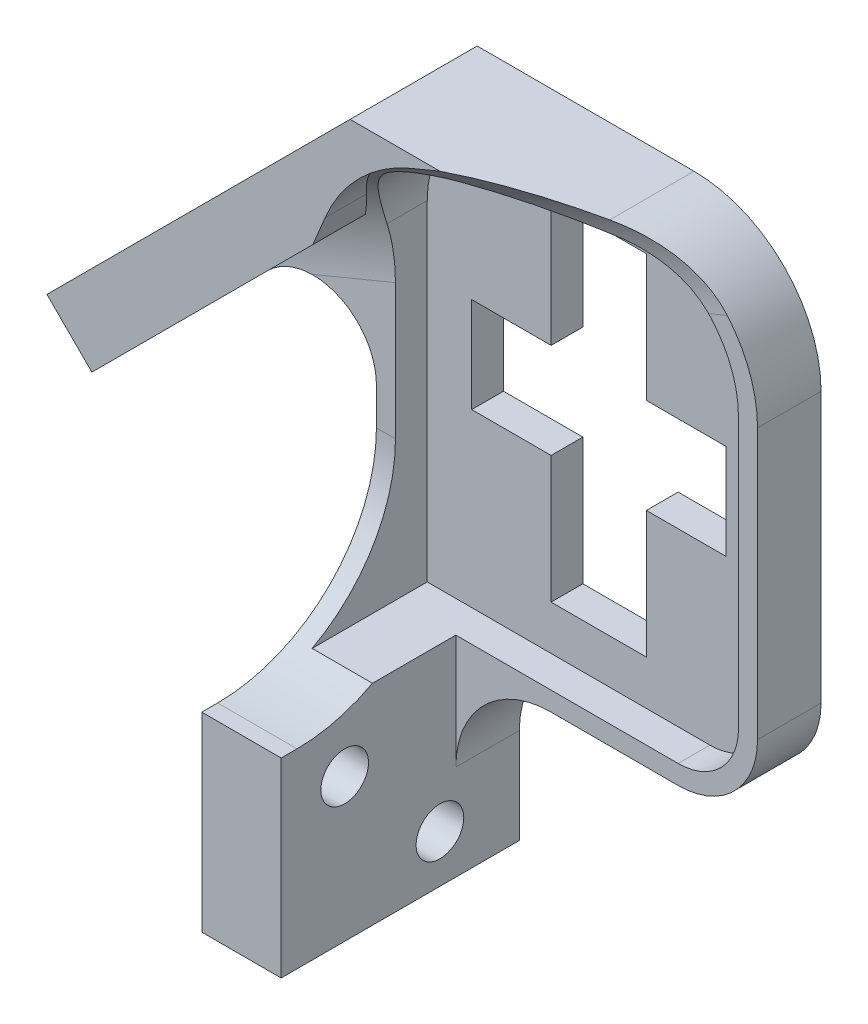
SolidWorks part; units mm, degrees
ref_plane "Front Plane" through (0, 0, 0) normal (0, 0, 1) x (1, 0, 0)
ref_plane "Top Plane" through (0, 0, 0) normal (0, 1, 0) x (1, 0, 0)
ref_plane "Right Plane" through (0, 0, 0) normal (1, 0, 0) x (0, 0, -1)
sketch "Sketch3" plane through (0, 0, 0) normal (0, 0, 1) x (1, 0, 0)
  line L0 (0, 10) -> (7, 10) construction
  line L1 (13, 4) -> (13, -13) construction
  line L2 (10, -16) -> (-7, -16) construction
  line L3 (-7, -16) -> (-7, 4) construction
  line L4 (-1, 10) -> (0, 10) construction
  line L5 (0, 0) -> (0, 10) construction
  line L6 (0, 12) -> (7, 12)
  line L7 (15, 4) -> (15, -13)
  line L8 (10, -18) -> (-9, -18)
  line L9 (-9, -18) -> (-9, 4)
  line L10 (-1, 12) -> (0, 12)
  arc A0 (13, 4) -> (7, 10) centre (7, 4) ccw construction
  arc A1 (-7, 4) -> (-1, 10) centre (-1, 4) cw construction
  arc A2 (10, -16) -> (13, -13) centre (10, -13) ccw construction
  arc A3 (15, 4) -> (7, 12) centre (7, 4) ccw
  arc A4 (10, -18) -> (15, -13) centre (10, -13) ccw
  arc A5 (-9, 4) -> (-1, 12) centre (-1, 4) cw
  point P9 (13, 10)
  point P12 (-7, 10)
  point P15 (13, -16)
  dimension "D5" = 6
  dimension "D6" = 3
  dimension "D1" = 10
  dimension "D2" = 26
  dimension "D3" = 20
  dimension "D4" = 7
  dimension "D7" = 2
extrude "Boss-Extrude4" add sketch "Sketch3" along normal blind 2
sketch "Sketch1" plane through (0, 0, 0) normal (0, 0, 1) x (1, 0, 0)
  line L0 (0, 0) -> (0, 8)
  line L1 (0, 8) -> (6, 8)
  line L2 (6, 8) -> (6, 0)
  line L3 (6, 0) -> (11, 0)
  line L4 (11, 0) -> (11, -6)
  line L5 (11, -6) -> (6, -6)
  line L6 (6, -6) -> (6, -14)
  line L7 (6, -14) -> (0, -14)
  line L8 (0, -14) -> (0, -6)
  line L9 (0, 0) -> (-5, 0)
  line L10 (-5, 0) -> (-5, -6)
  line L11 (-5, -6) -> (0, -6)
  dimension "D1" = 6
  dimension "D2" = 5
  dimension "D3" = 8
extrude "Cut-Extrude4" cut sketch "Sketch1" along normal blind 2
sketch "Sketch5" plane through (0, 0, 0) normal (0, 0, 1) x (1, 0, 0)
  line L0 (-9, -18) -> (-9, 4)
  line L2 (-9, -18) -> (10, -18)
  line L3 (-9, -18) -> (10, -18) construction
  line L4 (15, -13) -> (15, 4)
  line L5 (7, 12) -> (-1, 12)
  line L6 (7, 12) -> (-1, 12) construction
  line L7 (15, -13) -> (15, 4) construction
  line L8 (-7.8, -16.8) -> (-7.8, 4)
  line L9 (-7.8, -16.8) -> (10, -16.8)
  line L10 (13.8, -13) -> (13.8, 4)
  line L11 (7, 10.8) -> (-1, 10.8)
  arc A0 (-1, 12) -> (-9, 4) centre (-1, 4) ccw
  arc A1 (15, 4) -> (7, 12) centre (7, 4) ccw
  arc A2 (15, -13) -> (10, -18) centre (10, -13) cw
  arc A3 (-1, 10.8) -> (-7.8, 4) centre (-1, 4) ccw
  arc A4 (13.8, -13) -> (10, -16.8) centre (10, -13) cw
  arc A5 (13.8, 4) -> (7, 10.8) centre (7, 4) ccw
  point P18 (15, -18)
  dimension "D1" = 8
  dimension "D2" = 5
  dimension "D3" = 1.2
extrude "Boss-Extrude5" add sketch "Sketch5" along normal blind 4
sketch "Sketch6" plane through (0, -18, 0) normal (0, -1, 0) x (1, 0, 0)
  line L0 (-9, 0) -> (-4, 0)
  line L1 (-9, 0) -> (10, 0) construction
  line L2 (-4, 0) -> (-4, 15)
  line L3 (-9, 0) -> (-9, 15)
  line L4 (-9, 15) -> (-4, 15)
  dimension "D1" = 5
  dimension "D2" = 15
extrude "Boss-Extrude6" add sketch "Sketch6" along normal blind 12
fillet "Fillet1" radius 6 1 edges at (-4, -18, 2)
sketch "Sketch7" plane through (-4, 0, 0) normal (1, 0, 0) x (0, 0, -1)
  line L0 (-11, -21) -> (-5, -27) construction
  line L2 (-15, -30) -> (-15, -18) construction
  line L3 (-5, -27) -> (-11, -27) construction
  line L4 (-11, -27) -> (-11, -21) construction
  line L5 (-4, -18) -> (-15, -18) construction
  circle A0 centre (-11, -21) radius 1.5
  circle A1 centre (-5, -27) radius 1.5
  dimension "D1" = 3
  dimension "D2" = 6
  dimension "D3" = 3
  dimension "D4" = 45
  dimension "D6" = 4
extrude "Cut-Extrude5" cut sketch "Sketch7" against normal through all
fillet "Fillet3" radius 10 1 edges at (-6.5, -18, 4)
sketch "Sketch8" plane through (0, 0, 0) normal (0, 0, -1) x (-1, 0, 0)
  line L0 (9, 4) -> (22.9203, -9.9203)
  line L1 (9, 4) -> (9, -30) construction
  line L2 (22.9203, -9.9203) -> (25.7487, -7.0919)
  line L3 (25.7487, -7.0919) -> (6.6569, 12)
  line L4 (6.6569, 12) -> (1, 12)
  line L5 (1, 12) -> (6.6569, 9.6569)
  line L6 (6.6569, 9.6569) -> (9, 4)
  arc A4 (9, 4) -> (1, 12) centre (1, 4) ccw construction
  dimension "D1" = 45
  dimension "D2" = 4
  dimension "D3" = 27
extrude "Boss-Extrude8" add sketch "Sketch8" against normal blind 8 contours L5 L6 L0 L2 L3 L4
fillet "Fillet4" radius 10 2 edges at (-3.8284, 10.8284, 4) (-6.6569, 9.6569, 6)
sketch "Sketch9" plane through (-9.3284, 9.3284, 0) normal (-0.7071, 0.7071, 0) x (0, 0, 1)
  line L0 (4, -23.2218) -> (4, -18.2218) construction
  line L1 (8, -23.2218) -> (0, -23.2218) construction
  circle A0 centre (4, -18.2218) radius 1.5
  dimension "D1" = 3
  dimension "D2" = 5
extrude "Cut-Extrude7" cut sketch "Sketch9" against normal blind 8
fillet "Fillet6" radius 4 1 edges at (-9, 4, 2.349)
